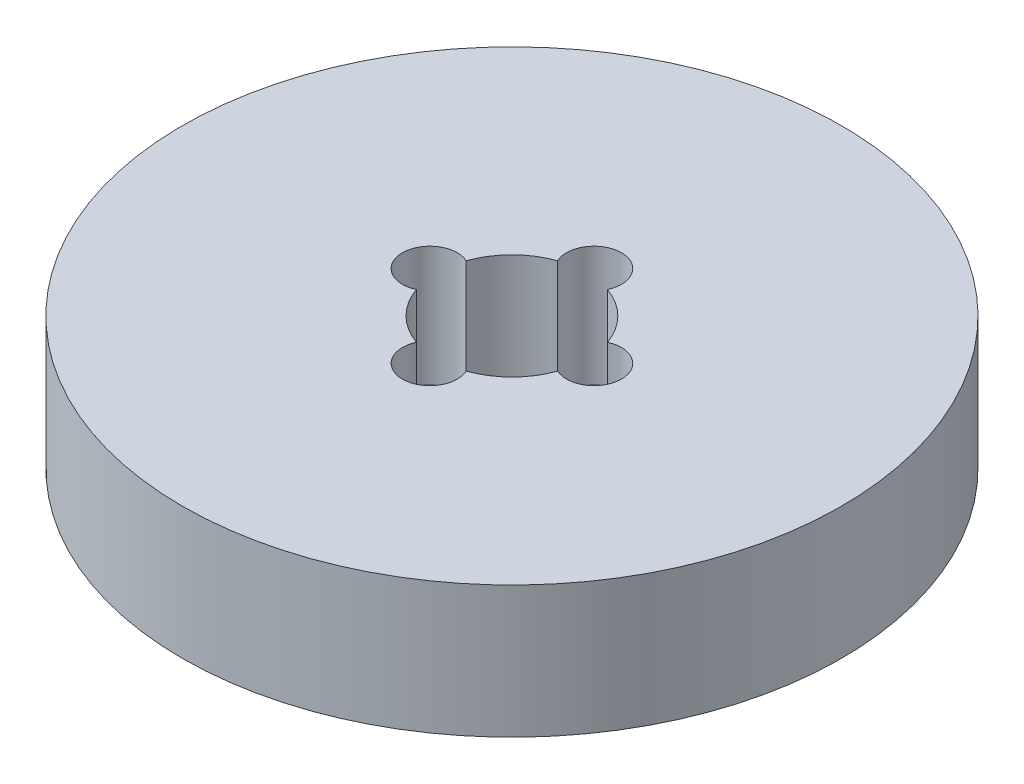
SolidWorks part; units mm, degrees
ref_plane "Front Plane" through (0, 0, 0) normal (0, 0, 1) x (1, 0, 0)
ref_plane "Top Plane" through (0, 0, 0) normal (0, 1, 0) x (1, 0, 0)
ref_plane "Right Plane" through (0, 0, 0) normal (1, 0, 0) x (0, 0, -1)
sketch "Sketch1" plane through (0, 0, 0) normal (0, 1, 0) x (1, 0, 0)
  circle A0 centre (0, 0) radius 55
  dimension "FLANGE_OD" = 110
extrude "Boss-Extrude1" add sketch "Sketch1" along normal blind 22
sketch "Sketch2" plane through (0, 0, 0) normal (0, 1, 0) x (1, 0, 0)
  circle A0 centre (0, 0) radius 12.5
  dimension "BORE_D" = 25
extrude "Cut-Extrude1" cut sketch "Sketch2" along normal through all
sketch "Sketch3" plane through (0, 22, 0) normal (0, 1, 0) x (1, 0, 0)
  circle A0 centre (0, 0) radius 13.6971 construction
  circle A1 centre (-13.6971, 0) radius 4.5757
  dimension "BOLT_D" = 9.1514
  dimension "BOLT_PCD" = 27.3941
extrude "Cut-Extrude2" cut sketch "Sketch3" against normal blind 20.0661
pattern_circular "CirPattern1" count 4 over 360 about axis through (0, 0, 0) along (0, 1, 0) of "Cut-Extrude2"
